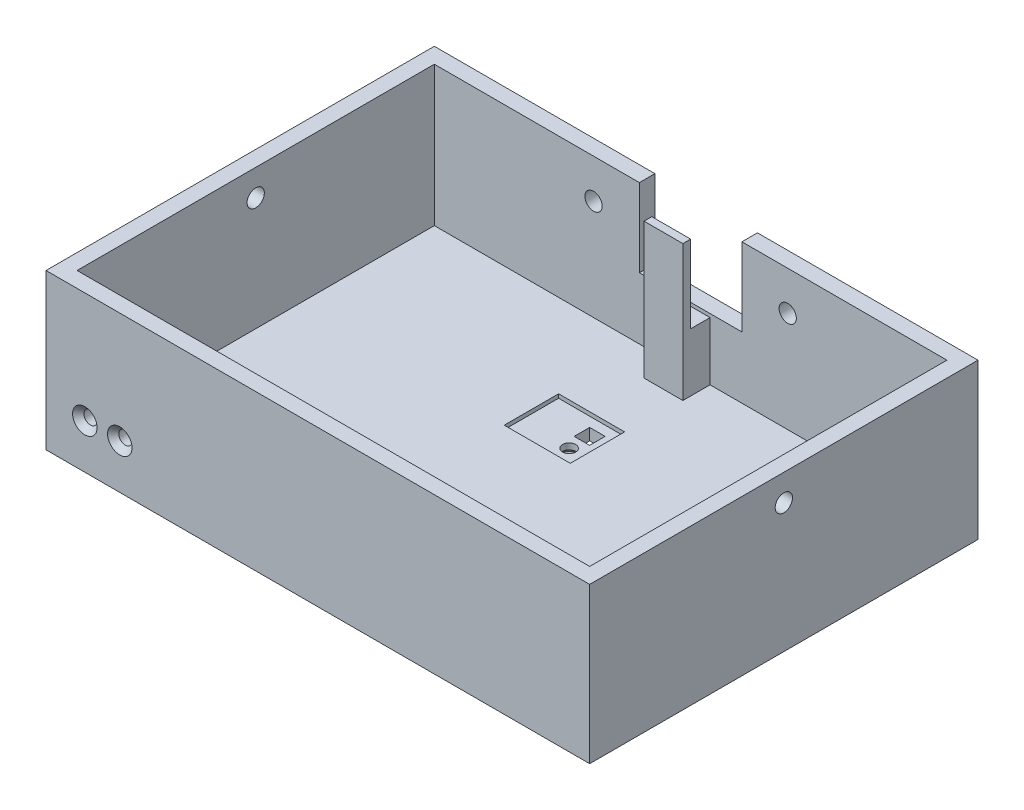
SolidWorks part; units mm, degrees
ref_plane "Спереди" through (0, 0, 0) normal (0, 0, 1) x (1, 0, 0)
ref_plane "Сверху" through (0, 0, 0) normal (0, 1, 0) x (1, 0, 0)
ref_plane "Справа" through (0, 0, 0) normal (1, 0, 0) x (0, 0, -1)
sketch "Эскиз1" plane through (0, 0, 0) normal (0, 1, 0) x (1, 0, 0)
  line L1 (70, 50) -> (-70, 50)
  line L2 (70, 50) -> (70, -50)
  line L3 (70, -50) -> (-70, -50)
  line L4 (-70, 50) -> (-70, -50)
  line L5 (70, 50) -> (-70, -50) construction
  line L6 (70, -50) -> (-70, 50) construction
  line L7 (66, 46) -> (-66, 46)
  line L8 (66, 46) -> (66, -46)
  line L9 (66, -46) -> (-66, -46)
  line L10 (-66, 46) -> (-66, -46)
  line L11 (66, 46) -> (-66, -46) construction
  line L12 (66, -46) -> (-66, 46) construction
  line L13 (-59.7, -44.8) -> (-51.3, -44.8)
  line L14 (-59.7, -44.8) -> (-59.7, -41.5)
  line L15 (-59.7, -41.5) -> (-51.3, -41.5)
  line L16 (-51.3, -44.8) -> (-51.3, -41.5)
  line L17 (-63, -46) -> (-48, -46)
  line L18 (-63, -46) -> (-63, -44.5)
  line L19 (-63, -44.5) -> (-48, -44.5)
  line L20 (-48, -46) -> (-48, -44.5)
  point P0 (0, 0)
  point P6 (0, 0)
  dimension "D1" = 140
  dimension "D2" = 100
  dimension "D3" = 4
  dimension "D4" = 4
  dimension "D5" = 1.2
  dimension "D6" = 3.3
  dimension "D7" = 8.4
  dimension "D8" = 15
  dimension "D9" = 3.3
  dimension "D10" = 1.5
  dimension "D11" = 3
  dimension "D12" = 3.3
extrude "Бобышка-Вытянуть2" add sketch "Эскиз1" along normal blind 4 contours L20 L9 L8 L7 L10 L18 L19 L14 L15 L16 | L1 L4 L3 L2 L10 L7 L8 L9 region at (68.2795, 0, 0) region at (0.2189, 0, -0.1737)
extrude "Бобышка-Вытянуть3" add sketch "Эскиз1<5>" along normal blind 2 contours L9 L20 L19 L13 L18 region at (-55.5, 0, 45.3257)
sketch "Эскиз1<5>" plane through (0, 0, 0) normal (0, 1, 0) x (1, 0, 0) same geometry as "Эскиз1"
extrude "Бобышка-Вытянуть4" add sketch "Эскиз1<6>" along normal blind 36 from surface contours L1 L4 L3 L2 L10 L7 L8 L9 region at (68.2795, 0, 0) starting at face at (-55.5, 4, 44.125)
sketch "Эскиз1<6>" plane through (0, 0, 0) normal (0, 1, 0) x (1, 0, 0) same geometry as "Эскиз1"
sketch "Эскиз2" plane through (0, 0, 46) normal (0, 0, -1) x (-1, 0, 0)
  line L0 (63, 11.5) -> (48, 11.5) construction
  line L1 (63, 4) -> (48, 4) construction
  line L2 (63, 4) -> (63, 17) construction
  line L3 (63, 17) -> (48, 17) construction
  line L4 (48, 4) -> (48, 17) construction
  line L5 (48, 2) -> (63, 2) construction
  line L6 (60, 11.5) -> (51, 11.5) construction
  circle A0 centre (60, 11.5) radius 2.025
  circle A1 centre (51, 11.5) radius 2.025
  point P12 (55.5, 11.5)
  dimension "D5" = 4.05
  dimension "D6" = 4.05
  dimension "D1" = 15
  dimension "D2" = 15
  dimension "D3" = 9.5
  dimension "D4" = 9
sketch "Эскиз4" plane through (0, 0, 50) normal (0, 0, 1) x (1, 0, 0)
  point P0 (-60, 11.5)
  point P2 (-51, 11.5)
hole_wizard "Зенковка для винта с потайной головкой M31" positions "Трехмерный эскиз2" profile "Эскиз5" countersink size "M3" standard "DIN" end condition up to next
sketch3d "Трехмерный эскиз2"
  point P0 (-51, 11.5, 50)
  point P3 (-60, 11.5, 50)
sketch "Эскиз5" plane through (-51, 11.5, 50) normal (1, 0, 0) x (0, -1, 0)
  line L0 (0, 0) -> (0, 4)
  line L1 (0, 4) -> (1.7, 4)
  line L2 (1.7, 4) -> (1.7, 1.45)
  line L3 (1.7, 1.45) -> (3.15, 0)
  line L5 (3.15, 0) -> (0, 0)
  line L6 (-1.7, 1.45) -> (-3.15, 0) construction
  line L11 (0, -6.35) -> (0, 107.95) construction
  dimension "Диаметр сквозного отверстия" = 3.4
  dimension "Глубина сквозного отверстия" = 4
  dimension "Диаметр передней зенковки" = 6.3
  dimension "Угол передней зенковки" = 90
sketch "Эскиз6" plane through (70, 0, 0) normal (1, 0, 0) x (0, 0, -1)
  line L0 (0, 40) -> (0, 33.2) construction
  line L1 (-50, 40) -> (50, 40) construction
  circle A0 centre (0, 33.2) radius 2.225
  dimension "D2" = 4.45
  dimension "D1" = 6.8
extrude "Вырез-Вытянуть1" cut sketch "Эскиз6" against normal up to next
mirror "Зеркальное отражение1" about plane through (0, 0, 0) normal (1, 0, 0) of "Вырез-Вытянуть1"
sketch "Эскиз7" plane through (0, 0, -50) normal (0, 0, -1) x (-1, 0, 0)
  line L0 (-13.2, 40) -> (13.2, 40)
  line L1 (70, 40) -> (-70, 40) construction
  line L2 (13.2, 40) -> (13.2, 19.9)
  line L3 (13.2, 19.9) -> (-13.2, 19.9)
  line L4 (-13.2, 19.9) -> (-13.2, 40)
  line L5 (-13.2, 19.9) -> (13.2, 40) construction
  line L19 (-16, 13.95) -> (16, 13.95) construction
  line L20 (-16, 13.95) -> (-16, 45.95) construction
  line L21 (-16, 45.95) -> (16, 45.95) construction
  line L22 (16, 13.95) -> (16, 45.95) construction
  line L23 (-16, 13.95) -> (16, 45.95) construction
  line L24 (-16, 45.95) -> (16, 13.95) construction
  line L28 (-16, 29.95) -> (-25, 29.95) construction
  line L29 (0, 13.95) -> (0, 47.2271) construction
  line L30 (16, 29.95) -> (25, 29.95) construction
  circle A0 centre (-25, 29.95) radius 2.225
  circle A1 centre (25, 29.95) radius 2.225
  point P5 (0, 40)
  point P28 (-25, 29.95)
  dimension "D9" = 4.45
  dimension "D1" = 26.4
  dimension "D2" = 20.1
  dimension "D7" = 32
  dimension "D8" = 9
extrude "Вырез-Вытянуть3" cut sketch "Эскиз7" against normal up to next contours L4 L0 L2 L3
extrude "Вырез-Вытянуть6" cut sketch "Эскиз7<9>" against normal up to next contours A0 | A1 region at (25, 29.95, -50)
sketch "Эскиз7<9>" plane through (0, 0, -50) normal (0, 0, -1) x (-1, 0, 0) same geometry as "Эскиз7"
sketch "Эскиз15" plane through (0, 0, 0) normal (0, -1, 0) x (1, 0, 0)
  line L0 (0, -50) -> (0, -20) construction
  line L1 (70, -50) -> (-70, -50) construction
  line L2 (0, -17.5) -> (0, -14.7) construction
  line L3 (-2.5, -22.5) -> (2.5, -22.5) construction
  line L4 (-2.5, -22.5) -> (-2.5, -17.5) construction
  line L5 (-2.5, -17.5) -> (2.5, -17.5) construction
  line L6 (2.5, -22.5) -> (2.5, -17.5) construction
  line L7 (-2.5, -22.5) -> (2.5, -17.5) construction
  line L8 (-2.5, -17.5) -> (2.5, -22.5) construction
  line L9 (-2, -22) -> (2, -22)
  line L10 (-2, -22) -> (-2, -18)
  line L11 (-2, -18) -> (2, -18)
  line L12 (2, -22) -> (2, -18)
  line L13 (-2, -22) -> (2, -18) construction
  line L14 (-2, -18) -> (2, -22) construction
  line L15 (-10.5, -22.5) -> (2.5, -12.5) construction
  line L16 (2.5, -22.5) -> (-10.5, -22.5) construction
  line L17 (2.5, -22.5) -> (2.5, -12.5) construction
  line L18 (2.5, -12.5) -> (-10.5, -12.5) construction
  line L19 (-10.5, -22.5) -> (-10.5, -12.5) construction
  line L21 (-12.5, -24.5) -> (4.5, -24.5)
  line L22 (-12.5, -24.5) -> (-12.5, -10.5)
  line L23 (-12.5, -10.5) -> (4.5, -10.5)
  line L24 (4.5, -24.5) -> (4.5, -10.5)
  line L25 (-12.5, -24.5) -> (4.5, -10.5) construction
  line L26 (-12.5, -10.5) -> (4.5, -24.5) construction
  point P18 (-4, -17.5)
  dimension "D1" = 30
  dimension "D2" = 5
  dimension "D3" = 4
  dimension "D4" = 2.8
  dimension "D5" = 13
  dimension "D6" = 10
  dimension "D7" = 17
  dimension "D8" = 14
hole_wizard "Зенковка для винта с потайной головкой M33" positions "Трехмерный эскиз8" profile "Эскиз16" countersink size "M3" standard "DIN" end condition up to next
sketch3d "Трехмерный эскиз8"
  point P0 (0, 0, -14.7)
sketch "Эскиз16" plane through (0, 0, -14.7) normal (1, 0, 0) x (0, 0, -1)
  line L0 (0, 0) -> (0, 4)
  line L1 (0, 4) -> (1.7, 4)
  line L2 (1.7, 4) -> (1.7, 1.45)
  line L3 (1.7, 1.45) -> (3.15, 0)
  line L5 (3.15, 0) -> (0, 0)
  line L6 (-1.7, 1.45) -> (-3.15, 0) construction
  line L11 (0, -6.35) -> (0, 107.95) construction
  dimension "Диаметр сквозного отверстия" = 3.4
  dimension "Глубина сквозного отверстия" = 4
  dimension "Диаметр передней зенковки" = 6.3
  dimension "Угол передней зенковки" = 90
extrude "Вырез-Вытянуть8" cut sketch "Эскиз15" against normal up to next contours L9 L12 L11 L10 region at (0, 0, -20)
extrude "Вырез-Вытянуть9" cut sketch "Эскиз15<4>" against normal up to next from offset 3 offset against normal yes
sketch "Эскиз15<4>" plane through (0, 0, 0) normal (0, -1, 0) x (1, 0, 0) same geometry as "Эскиз15"
sketch "Эскиз20" plane through (0, 0, 0) normal (0, -1, 0) x (1, 0, 0)
  line L0 (0, -50) -> (0, -46) construction
  line L1 (70, -50) -> (-70, -50) construction
  line L2 (-5, -46) -> (5, -46)
  line L4 (5, -46) -> (-5, -46)
  line L5 (5, -46) -> (5, -39)
  line L6 (5, -39) -> (-5, -39)
  line L7 (-5, -46) -> (-5, -39)
  line L8 (5, -39) -> (-5, -39)
  line L9 (5, -39) -> (5, -41)
  line L10 (5, -41) -> (-5, -41)
  line L11 (-5, -39) -> (-5, -41)
  point P8 (0, -46)
  dimension "D1" = 4
  dimension "D2" = 10
  dimension "D3" = 7
  dimension "D4" = 2
extrude "Бобышка-Вытянуть7" add sketch "Эскиз20" against normal blind 15 from surface contours L5 L10 L7 L2 L4 | L10 L5 L6 L7 region at (0, 0, -43.5) region at (0, 0, -40) starting at face at (-4, 4, -17.5)
extrude "Бобышка-Вытянуть8" add sketch "Эскиз20<3>" against normal blind 20 from surface contours L10 L5 L6 L7 region at (0, 0, -40) starting at face at (0, 19, -42.5)
sketch "Эскиз20<3>" plane through (0, 0, 0) normal (0, -1, 0) x (1, 0, 0) same geometry as "Эскиз20"
sketch "Эскиз21" plane through (0, 0, 0) normal (0, -1, 0) x (1, 0, 0)
  line L0 (0, 50) -> (0, 30) construction
  line L1 (70, 50) -> (-70, 50) construction
  line L2 (-35, 30) -> (35, 30) construction
  text T0 "MADE BY \r\nFEANOR19 & TIFOMEI" font "Century Gothic" height in points 14
  point P8 (0, 30)
  dimension "D1" = 20
  dimension "D2" = 70
extrude "Вырез-Вытянуть10" cut sketch "Эскиз21" against normal blind 1
